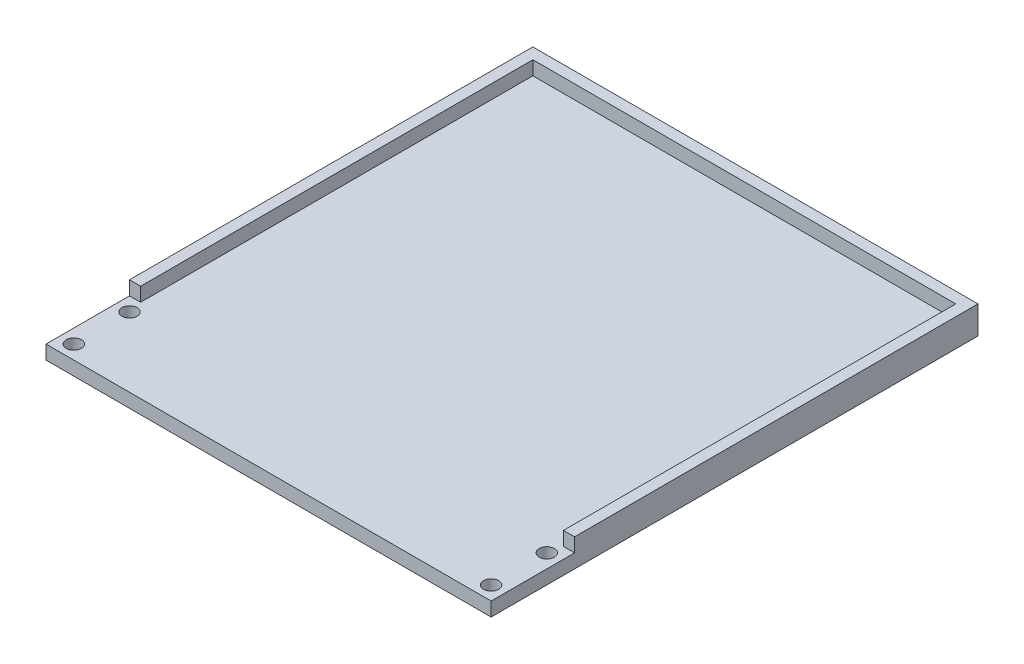
SolidWorks part; units mm, degrees
material "ABS"
ref_plane "Front Plane" through (0, 0, 0) normal (0, 0, 1) x (1, 0, 0)
ref_plane "Top Plane" through (0, 0, 0) normal (0, 1, 0) x (1, 0, 0)
ref_plane "Right Plane" through (0, 0, 0) normal (1, 0, 0) x (0, 0, -1)
other "Center of Mass"
sketch "Sketch1" plane through (0, 0, 0) normal (0, 1, 0) x (1, 0, 0)
  line L0 (-44.45, -60.325) -> (44.45, -60.325)
  line L1 (-50.8, -50.8) -> (50.8, -50.8)
  line L2 (-50.8, -50.8) -> (-50.8, 50.8)
  line L3 (-50.8, 50.8) -> (50.8, 50.8)
  line L4 (50.8, -50.8) -> (50.8, 50.8)
  line L5 (-50.8, -50.8) -> (50.8, 50.8) construction
  line L6 (-50.8, 50.8) -> (50.8, -50.8) construction
  line L7 (-50.8, -50.8) -> (-44.45, -50.8)
  line L8 (-50.8, -50.8) -> (-50.8, -60.325)
  line L9 (-50.8, -60.325) -> (-44.45, -60.325)
  line L10 (-44.45, -50.8) -> (-44.45, -60.325)
  line L11 (50.8, -50.8) -> (44.45, -50.8)
  line L12 (50.8, -50.8) -> (50.8, -60.325)
  line L13 (50.8, -60.325) -> (44.45, -60.325)
  line L14 (44.45, -50.8) -> (44.45, -60.325)
  point P0 (0, 0)
  dimension "D1" = 101.6
  dimension "D2" = 101.6
  dimension "D3" = 9.525
  dimension "D4" = 6.35
extrude "Boss-Extrude1" add sketch "Sketch1" along normal blind 3.175 contours L1 L4 L3 L2 | L10 L1 L8 L9 | L1 L14 L13 L12 region at (-47.625, 0, 55.5625) region at (47.625, 0, 55.5625) region at (0, 0, 0)
hole_wizard "#8-32 Tapped Hole1" positions "Sketch6" profile "Sketch7" tap size "#8-32" standard "ANSI Inch" end condition through all
sketch "Sketch6" plane through (0, 0, 0) normal (0, -1, 0) x (-1, 0, 0)
  line L0 (-47.625, -44.45) -> (-47.625, -57.15) construction
  line L2 (47.625, -44.45) -> (47.625, -57.15) construction
  line L3 (44.45, -50.8) -> (47.625, -50.8) construction
  line L4 (47.625, -50.8) -> (50.8, -50.8) construction
  line L5 (50.8, -60.325) -> (50.8, 50.8) construction
  line L7 (44.45, -50.8) -> (-44.45, -50.8) construction
  line L8 (-44.45, -50.8) -> (-47.625, -50.8) construction
  line L9 (-47.625, -50.8) -> (-50.8, -50.8) construction
  line L10 (-50.8, -60.325) -> (-50.8, 50.8) construction
  point P0 (-47.625, -57.15)
  point P2 (-47.625, -44.45)
  point P4 (47.625, -57.15)
  point P6 (47.625, -44.45)
  point P37 (-47.625, -57.0069)
  point P38 (-47.625, -57.4673)
  dimension "D1" = 12.7
sketch "Sketch7" plane through (47.625, 0, 57.15) normal (1, 0, 0) x (0, 0, -1)
  line L0 (0, 0) -> (0, 3.175)
  line L1 (0, 3.175) -> (1.7272, 3.175)
  line L2 (1.7272, 3.175) -> (1.7272, 0)
  line L5 (1.7272, 0) -> (0, 0)
  line L11 (0, -6.35) -> (0, 107.95) construction
  dimension "Thru Tap Drill Dia." = 3.4544
  dimension "Thru Tap Drill Depth" = 3.175
cosmetic thread "Hole Thread1" parameters "D2"=4.1656
cosmetic thread "Hole Thread2" parameters "D2"=4.1656
cosmetic thread "Hole Thread3" parameters "D2"=4.1656
cosmetic thread "Hole Thread4" parameters "D2"=4.1656
sketch "Sketch8" plane through (0, 3.175, 0) normal (0, 1, 0) x (1, 0, 0)
  line L6 (-50.8, 50.8) -> (50.8, 50.8)
  line L7 (50.8, 50.8) -> (50.8, -41.275)
  line L8 (50.8, -60.325) -> (50.8, 50.8) construction
  line L9 (48.26, 48.26) -> (48.26, -60.325)
  line L10 (-48.26, 48.26) -> (48.26, 48.26)
  line L11 (-48.26, -60.325) -> (-48.26, 48.26)
  line L12 (48.26, 48.26) -> (48.26, -41.275)
  line L13 (-48.26, 48.26) -> (48.26, 48.26)
  line L14 (-48.26, -41.275) -> (-48.26, 48.26)
  line L15 (50.8, -41.275) -> (48.26, -41.275)
  line L16 (-48.26, -41.275) -> (-50.8, -41.275)
  line L17 (-50.8, -60.325) -> (-50.8, 50.8) construction
  line L18 (-50.8, 50.8) -> (-50.8, -41.275)
  line L19 (-44.45, -50.8) -> (-44.45, -41.275) construction
  line L20 (-44.45, -41.275) -> (-48.26, -41.275) construction
  line L21 (-44.45, -50.8) -> (-44.45, -60.325) construction
  line L22 (-48.26, -60.325) -> (-48.26, -41.275) construction
  line L23 (48.26, -41.275) -> (48.26, -60.325) construction
  point P13 (-44.45, -37.5333)
  dimension "D1" = 2.54
extrude "Boss-Extrude2" add sketch "Sketch8" along normal blind 3.175
extrude "Boss-Extrude3" add sketch "Sketch1<3>" along normal up to surface (3.175 mm away) contours L14 L1 L10 L0 region at (0, 0, 55.5625) up to face at (0, 3.175, 34.29)
sketch "Sketch1<3>" plane through (0, 0, 0) normal (0, 1, 0) x (1, 0, 0) same geometry as "Sketch1"
